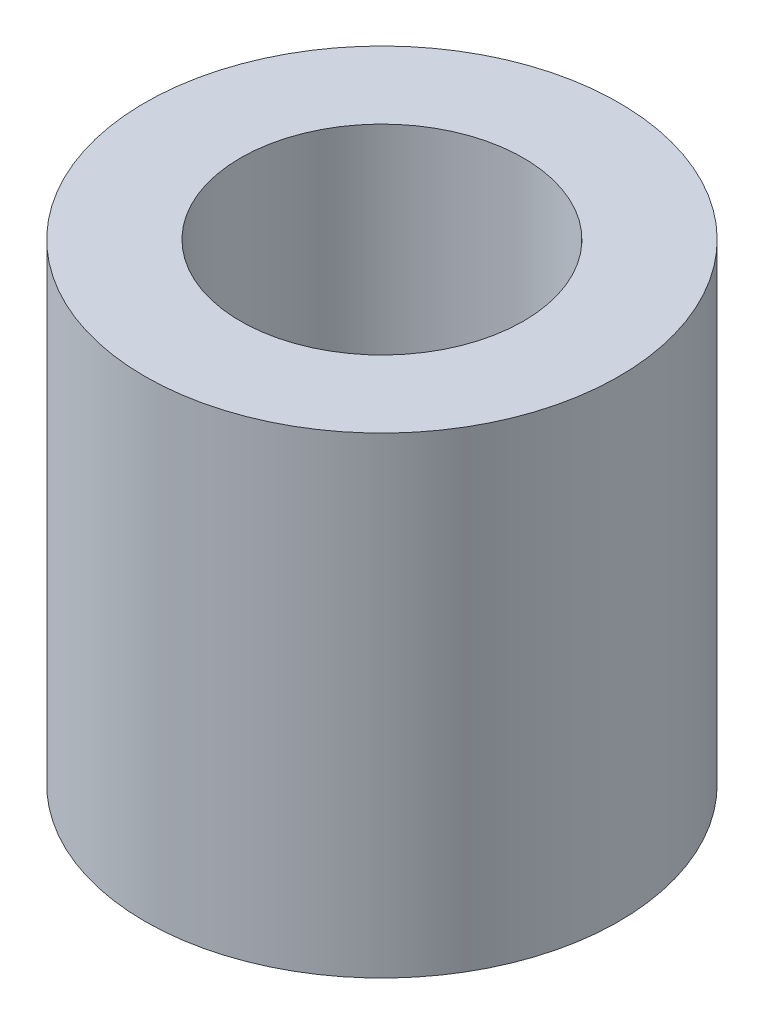
SolidWorks part; units mm, degrees
ref_plane "Front Plane" through (0, 0, 0) normal (0, 0, 1) x (1, 0, 0)
ref_plane "Top Plane" through (0, 0, 0) normal (0, 1, 0) x (1, 0, 0)
ref_plane "Right Plane" through (0, 0, 0) normal (1, 0, 0) x (0, 0, -1)
sketch "Sketch1" plane through (0, 0, 0) normal (0, 1, 0) x (1, 0, 0)
  circle A0 centre (0, 0) radius 15
  dimension "D1" = 29.9999
extrude "Extrude-Thin1" add sketch "Sketch1" along normal blind 29.8628 thin thin type one direction reverse wall 6.0503
